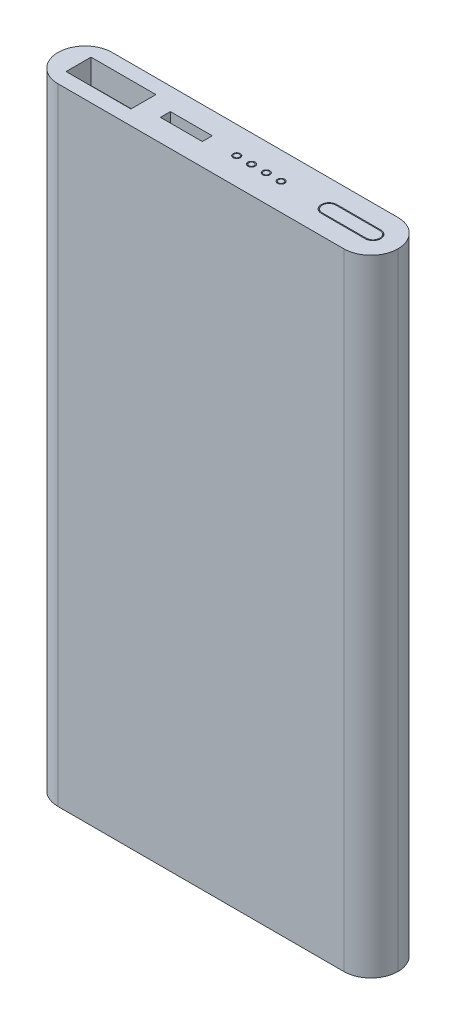
SolidWorks part; units mm, degrees
material "6061 Alloy"
ref_plane "Front Plane" through (0, 0, 0) normal (0, 0, 1) x (1, 0, 0)
ref_plane "Top Plane" through (0, 0, 0) normal (0, 1, 0) x (1, 0, 0)
ref_plane "Right Plane" through (0, 0, 0) normal (1, 0, 0) x (0, 0, -1)
sketch "Sketch1" plane through (0, 0, 0) normal (0, 1, 0) x (1, 0, 0)
  line L1 (0, 0) -> (69, 0)
  line L2 (0, 0) -> (0, 11)
  line L3 (0, 11) -> (69, 11)
  line L4 (69, 0) -> (69, 11)
  dimension "D1" = 11
  dimension "D2" = 69
extrude "Boss-Extrude1" add sketch "Sketch1" along normal blind 127
fillet "Fillet1" radius 5.5 4 edges at (69, 63.5, 0) (69, 63.5, -11) (0, 63.5, -11) (0, 63.5, 0)
sketch "Sketch2" plane through (0, 127, 0) normal (0, 1, 0) x (1, 0, 0)
  line L0 (0, 5.5) -> (69, 5.5) construction
  line L1 (55.0035, 5.5) -> (63.9137, 5.5) construction
  line L2 (4.175, 8.0313) -> (17.3378, 8.0313)
  line L3 (4.175, 8.0313) -> (4.175, 2.9687)
  line L4 (4.175, 2.9687) -> (17.3378, 2.9687)
  line L5 (17.3378, 8.0313) -> (17.3378, 2.9687)
  line L6 (4.175, 8.0313) -> (17.3378, 2.9687) construction
  line L7 (4.175, 2.9687) -> (17.3378, 8.0313) construction
  line L8 (21.7929, 6.5125) -> (30.298, 6.5125)
  line L9 (21.7929, 6.5125) -> (21.7929, 4.4875)
  line L10 (21.7929, 4.4875) -> (30.298, 4.4875)
  line L11 (30.298, 6.5125) -> (30.298, 4.4875)
  line L12 (21.7929, 6.5125) -> (30.298, 4.4875) construction
  line L13 (21.7929, 4.4875) -> (30.298, 6.5125) construction
  line L14 (55.0035, 7.0694) -> (63.9137, 7.0694)
  line L15 (55.0035, 3.9306) -> (63.9137, 3.9306)
  arc A0 (55.0035, 7.0694) -> (55.0035, 3.9306) centre (55.0035, 5.5) ccw
  arc A1 (63.9137, 3.9306) -> (63.9137, 7.0694) centre (63.9137, 5.5) ccw
  circle A2 centre (36.2719, 5.5) radius 0.7301
  circle A3 centre (39.2719, 5.5) radius 0.7301
  circle A4 centre (42.2719, 5.5) radius 0.7301
  circle A5 centre (45.2719, 5.5) radius 0.7301
  point P4 (10.7564, 5.5)
  point P9 (26.0455, 5.5)
  point P16 (59.4586, 5.5)
extrude "Cut-Extrude1" cut sketch "Sketch2" against normal blind 5
sketch "Sketch3" plane through (0, 122, 0) normal (0, 1, 0) x (1, 0, 0)
  line L4 (55.0035, 4.1306) -> (63.9137, 4.1306)
  line L5 (63.9137, 6.8694) -> (55.0035, 6.8694)
  line L6 (55.0035, 4.1306) -> (63.9137, 4.1306)
  line L7 (63.9137, 6.8694) -> (55.0035, 6.8694)
  circle A3 centre (36.2719, 5.5) radius 0.5301
  arc A4 (55.0035, 6.8694) -> (55.0035, 4.1306) centre (55.0035, 5.5) ccw
  arc A5 (63.9137, 4.1306) -> (63.9137, 6.8694) centre (63.9137, 5.5) ccw
  arc A6 (55.0035, 6.8694) -> (55.0035, 4.1306) centre (55.0035, 5.5) ccw
  arc A7 (63.9137, 4.1306) -> (63.9137, 6.8694) centre (63.9137, 5.5) ccw
  circle A8 centre (36.2719, 5.5) radius 0.5301
  circle A10 centre (39.2719, 5.5) radius 0.5301
  circle A11 centre (39.2719, 5.5) radius 0.5301
  circle A13 centre (42.2719, 5.5) radius 0.5301
  circle A14 centre (42.2719, 5.5) radius 0.5301
  circle A16 centre (45.2719, 5.5) radius 0.5301
  circle A17 centre (45.2719, 5.5) radius 0.5301
  dimension "D1" = 0.2
  dimension "D2" = 0.2
  dimension "D3" = 0.2
  dimension "D4" = 0.2
  dimension "D5" = 0.2
extrude "Boss-Extrude2" add sketch "Sketch3" along normal up to surface (5 mm away) up to face at (10.7564, 127, -5.5)
ref_plane "Plane1" through (34.5, 0, 0) normal (-1, 0, 0) x (0, 0, 1)
